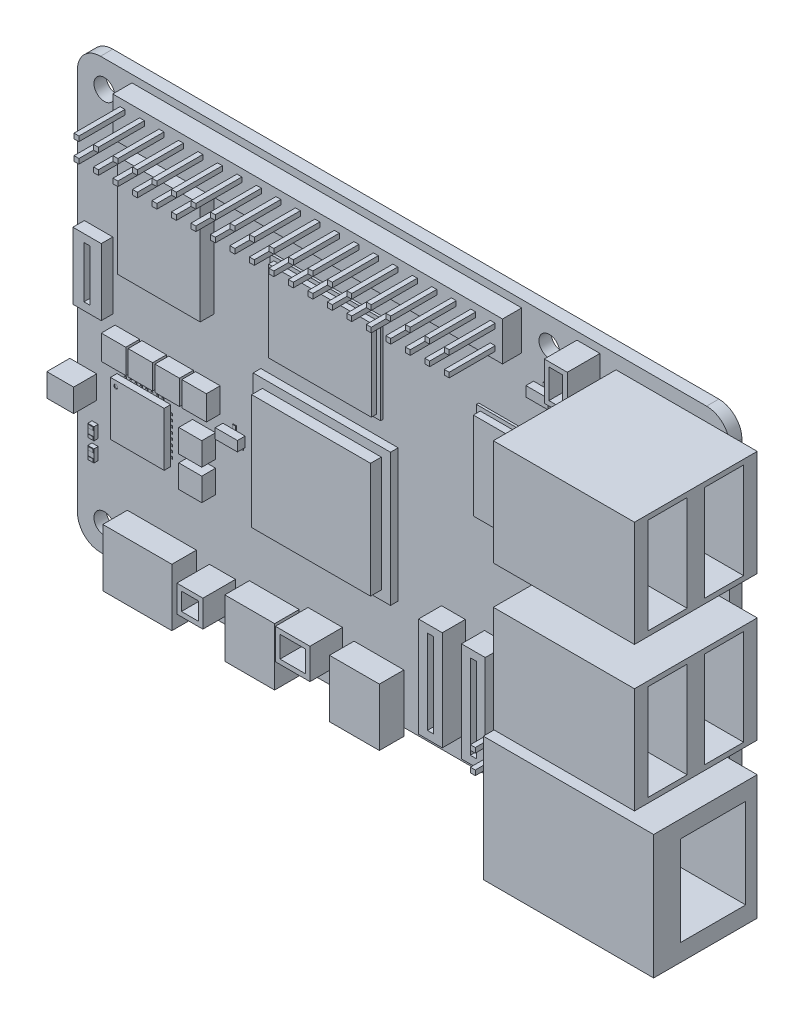
SolidWorks part; units mm, degrees
ref_plane "Front Plane" through (0, 0, 0) normal (0, 0, 1) x (1, 0, 0)
ref_plane "Top Plane" through (0, 0, 0) normal (0, 1, 0) x (1, 0, 0)
ref_plane "Right Plane" through (0, 0, 0) normal (1, 0, 0) x (0, 0, -1)
sketch "Sketch1" plane through (0, 0, 0) normal (0, 0, 1) x (1, 0, 0)
  line L0 (3, 0) -> (82, 0)
  line L1 (85, 3) -> (85, 53)
  line L2 (82, 56) -> (3, 56)
  line L3 (0, 53) -> (0, 3)
  arc A0 (82, 0) -> (85, 3) centre (82, 3) ccw
  arc A1 (85, 53) -> (82, 56) centre (82, 53) ccw
  arc A2 (3, 56) -> (0, 53) centre (3, 53) ccw
  arc A3 (0, 3) -> (3, 0) centre (3, 3) ccw
extrude "PCB" add sketch "Sketch1" along normal blind 1.6
ref_plane "Plane_z1_6" through (0, 0, 1.6) normal (0, 0, 1) x (1, 0, 0)
sketch "Sketch2" plane through (0, 0, 1.6) normal (0, 0, 1) x (1, 0, 0)
  line L1 (7.1, 49.96) -> (57.9, 49.96)
  line L2 (7.1, 49.96) -> (7.1, 55.04)
  line L3 (7.1, 55.04) -> (57.9, 55.04)
  line L4 (57.9, 49.96) -> (57.9, 55.04)
  line L6 (58.76, 6.76) -> (63.84, 6.76)
  line L7 (58.76, 6.76) -> (58.76, 11.84)
  line L8 (58.76, 11.84) -> (63.84, 11.84)
  line L9 (63.84, 6.76) -> (63.84, 11.84)
extrude "Header_Blocks" add sketch "Sketch2" along normal blind 2.5
ref_plane "Plane_z4_1" through (0, 0, 4.1) normal (0, 0, 1) x (1, 0, 0)
sketch "Sketch3" plane through (0, 0, 4.1) normal (0, 0, 1) x (1, 0, 0)
  line L1 (8.05, 50.91) -> (8.69, 50.91)
  line L2 (8.05, 50.91) -> (8.05, 51.55)
  line L3 (8.05, 51.55) -> (8.69, 51.55)
  line L4 (8.69, 50.91) -> (8.69, 51.55)
  line L6 (8.05, 53.45) -> (8.69, 53.45)
  line L7 (8.05, 53.45) -> (8.05, 54.09)
  line L8 (8.05, 54.09) -> (8.69, 54.09)
  line L9 (8.69, 53.45) -> (8.69, 54.09)
  line L11 (10.59, 50.91) -> (11.23, 50.91)
  line L12 (10.59, 50.91) -> (10.59, 51.55)
  line L13 (10.59, 51.55) -> (11.23, 51.55)
  line L14 (11.23, 50.91) -> (11.23, 51.55)
  line L16 (10.59, 53.45) -> (11.23, 53.45)
  line L17 (10.59, 53.45) -> (10.59, 54.09)
  line L18 (10.59, 54.09) -> (11.23, 54.09)
  line L19 (11.23, 53.45) -> (11.23, 54.09)
  line L21 (13.13, 50.91) -> (13.77, 50.91)
  line L22 (13.13, 50.91) -> (13.13, 51.55)
  line L23 (13.13, 51.55) -> (13.77, 51.55)
  line L24 (13.77, 50.91) -> (13.77, 51.55)
  line L26 (13.13, 53.45) -> (13.77, 53.45)
  line L27 (13.13, 53.45) -> (13.13, 54.09)
  line L28 (13.13, 54.09) -> (13.77, 54.09)
  line L29 (13.77, 53.45) -> (13.77, 54.09)
  line L31 (15.67, 50.91) -> (16.31, 50.91)
  line L32 (15.67, 50.91) -> (15.67, 51.55)
  line L33 (15.67, 51.55) -> (16.31, 51.55)
  line L34 (16.31, 50.91) -> (16.31, 51.55)
  line L36 (15.67, 53.45) -> (16.31, 53.45)
  line L37 (15.67, 53.45) -> (15.67, 54.09)
  line L38 (15.67, 54.09) -> (16.31, 54.09)
  line L39 (16.31, 53.45) -> (16.31, 54.09)
  line L41 (18.21, 50.91) -> (18.85, 50.91)
  line L42 (18.21, 50.91) -> (18.21, 51.55)
  line L43 (18.21, 51.55) -> (18.85, 51.55)
  line L44 (18.85, 50.91) -> (18.85, 51.55)
  line L46 (18.21, 53.45) -> (18.85, 53.45)
  line L47 (18.21, 53.45) -> (18.21, 54.09)
  line L48 (18.21, 54.09) -> (18.85, 54.09)
  line L49 (18.85, 53.45) -> (18.85, 54.09)
  line L51 (20.75, 50.91) -> (21.39, 50.91)
  line L52 (20.75, 50.91) -> (20.75, 51.55)
  line L53 (20.75, 51.55) -> (21.39, 51.55)
  line L54 (21.39, 50.91) -> (21.39, 51.55)
  line L56 (20.75, 53.45) -> (21.39, 53.45)
  line L57 (20.75, 53.45) -> (20.75, 54.09)
  line L58 (20.75, 54.09) -> (21.39, 54.09)
  line L59 (21.39, 53.45) -> (21.39, 54.09)
  line L61 (23.29, 50.91) -> (23.93, 50.91)
  line L62 (23.29, 50.91) -> (23.29, 51.55)
  line L63 (23.29, 51.55) -> (23.93, 51.55)
  line L64 (23.93, 50.91) -> (23.93, 51.55)
  line L66 (23.29, 53.45) -> (23.93, 53.45)
  line L67 (23.29, 53.45) -> (23.29, 54.09)
  line L68 (23.29, 54.09) -> (23.93, 54.09)
  line L69 (23.93, 53.45) -> (23.93, 54.09)
  line L71 (25.83, 50.91) -> (26.47, 50.91)
  line L72 (25.83, 50.91) -> (25.83, 51.55)
  line L73 (25.83, 51.55) -> (26.47, 51.55)
  line L74 (26.47, 50.91) -> (26.47, 51.55)
  line L76 (25.83, 53.45) -> (26.47, 53.45)
  line L77 (25.83, 53.45) -> (25.83, 54.09)
  line L78 (25.83, 54.09) -> (26.47, 54.09)
  line L79 (26.47, 53.45) -> (26.47, 54.09)
  line L81 (28.37, 50.91) -> (29.01, 50.91)
  line L82 (28.37, 50.91) -> (28.37, 51.55)
  line L83 (28.37, 51.55) -> (29.01, 51.55)
  line L84 (29.01, 50.91) -> (29.01, 51.55)
  line L86 (28.37, 53.45) -> (29.01, 53.45)
  line L87 (28.37, 53.45) -> (28.37, 54.09)
  line L88 (28.37, 54.09) -> (29.01, 54.09)
  line L89 (29.01, 53.45) -> (29.01, 54.09)
  line L91 (30.91, 50.91) -> (31.55, 50.91)
  line L92 (30.91, 50.91) -> (30.91, 51.55)
  line L93 (30.91, 51.55) -> (31.55, 51.55)
  line L94 (31.55, 50.91) -> (31.55, 51.55)
  line L96 (30.91, 53.45) -> (31.55, 53.45)
  line L97 (30.91, 53.45) -> (30.91, 54.09)
  line L98 (30.91, 54.09) -> (31.55, 54.09)
  line L99 (31.55, 53.45) -> (31.55, 54.09)
  line L101 (33.45, 50.91) -> (34.09, 50.91)
  line L102 (33.45, 50.91) -> (33.45, 51.55)
  line L103 (33.45, 51.55) -> (34.09, 51.55)
  line L104 (34.09, 50.91) -> (34.09, 51.55)
  line L106 (33.45, 53.45) -> (34.09, 53.45)
  line L107 (33.45, 53.45) -> (33.45, 54.09)
  line L108 (33.45, 54.09) -> (34.09, 54.09)
  line L109 (34.09, 53.45) -> (34.09, 54.09)
  line L111 (35.99, 50.91) -> (36.63, 50.91)
  line L112 (35.99, 50.91) -> (35.99, 51.55)
  line L113 (35.99, 51.55) -> (36.63, 51.55)
  line L114 (36.63, 50.91) -> (36.63, 51.55)
  line L116 (35.99, 53.45) -> (36.63, 53.45)
  line L117 (35.99, 53.45) -> (35.99, 54.09)
  line L118 (35.99, 54.09) -> (36.63, 54.09)
  line L119 (36.63, 53.45) -> (36.63, 54.09)
  line L121 (38.53, 50.91) -> (39.17, 50.91)
  line L122 (38.53, 50.91) -> (38.53, 51.55)
  line L123 (38.53, 51.55) -> (39.17, 51.55)
  line L124 (39.17, 50.91) -> (39.17, 51.55)
  line L126 (38.53, 53.45) -> (39.17, 53.45)
  line L127 (38.53, 53.45) -> (38.53, 54.09)
  line L128 (38.53, 54.09) -> (39.17, 54.09)
  line L129 (39.17, 53.45) -> (39.17, 54.09)
  line L131 (41.07, 50.91) -> (41.71, 50.91)
  line L132 (41.07, 50.91) -> (41.07, 51.55)
  line L133 (41.07, 51.55) -> (41.71, 51.55)
  line L134 (41.71, 50.91) -> (41.71, 51.55)
  line L136 (41.07, 53.45) -> (41.71, 53.45)
  line L137 (41.07, 53.45) -> (41.07, 54.09)
  line L138 (41.07, 54.09) -> (41.71, 54.09)
  line L139 (41.71, 53.45) -> (41.71, 54.09)
  line L141 (43.61, 50.91) -> (44.25, 50.91)
  line L142 (43.61, 50.91) -> (43.61, 51.55)
  line L143 (43.61, 51.55) -> (44.25, 51.55)
  line L144 (44.25, 50.91) -> (44.25, 51.55)
  line L146 (43.61, 53.45) -> (44.25, 53.45)
  line L147 (43.61, 53.45) -> (43.61, 54.09)
  line L148 (43.61, 54.09) -> (44.25, 54.09)
  line L149 (44.25, 53.45) -> (44.25, 54.09)
  line L151 (46.15, 50.91) -> (46.79, 50.91)
  line L152 (46.15, 50.91) -> (46.15, 51.55)
  line L153 (46.15, 51.55) -> (46.79, 51.55)
  line L154 (46.79, 50.91) -> (46.79, 51.55)
  line L156 (46.15, 53.45) -> (46.79, 53.45)
  line L157 (46.15, 53.45) -> (46.15, 54.09)
  line L158 (46.15, 54.09) -> (46.79, 54.09)
  line L159 (46.79, 53.45) -> (46.79, 54.09)
  line L161 (48.69, 50.91) -> (49.33, 50.91)
  line L162 (48.69, 50.91) -> (48.69, 51.55)
  line L163 (48.69, 51.55) -> (49.33, 51.55)
  line L164 (49.33, 50.91) -> (49.33, 51.55)
  line L166 (48.69, 53.45) -> (49.33, 53.45)
  line L167 (48.69, 53.45) -> (48.69, 54.09)
  line L168 (48.69, 54.09) -> (49.33, 54.09)
  line L169 (49.33, 53.45) -> (49.33, 54.09)
  line L171 (51.23, 50.91) -> (51.87, 50.91)
  line L172 (51.23, 50.91) -> (51.23, 51.55)
  line L173 (51.23, 51.55) -> (51.87, 51.55)
  line L174 (51.87, 50.91) -> (51.87, 51.55)
  line L176 (51.23, 53.45) -> (51.87, 53.45)
  line L177 (51.23, 53.45) -> (51.23, 54.09)
  line L178 (51.23, 54.09) -> (51.87, 54.09)
  line L179 (51.87, 53.45) -> (51.87, 54.09)
  line L181 (53.77, 50.91) -> (54.41, 50.91)
  line L182 (53.77, 50.91) -> (53.77, 51.55)
  line L183 (53.77, 51.55) -> (54.41, 51.55)
  line L184 (54.41, 50.91) -> (54.41, 51.55)
  line L186 (53.77, 53.45) -> (54.41, 53.45)
  line L187 (53.77, 53.45) -> (53.77, 54.09)
  line L188 (53.77, 54.09) -> (54.41, 54.09)
  line L189 (54.41, 53.45) -> (54.41, 54.09)
  line L191 (56.31, 50.91) -> (56.95, 50.91)
  line L192 (56.31, 50.91) -> (56.31, 51.55)
  line L193 (56.31, 51.55) -> (56.95, 51.55)
  line L194 (56.95, 50.91) -> (56.95, 51.55)
  line L196 (56.31, 53.45) -> (56.95, 53.45)
  line L197 (56.31, 53.45) -> (56.31, 54.09)
  line L198 (56.31, 54.09) -> (56.95, 54.09)
  line L199 (56.95, 53.45) -> (56.95, 54.09)
  line L201 (59.71, 7.71) -> (60.35, 7.71)
  line L202 (59.71, 7.71) -> (59.71, 8.35)
  line L203 (59.71, 8.35) -> (60.35, 8.35)
  line L204 (60.35, 7.71) -> (60.35, 8.35)
  line L206 (59.71, 10.25) -> (60.35, 10.25)
  line L207 (59.71, 10.25) -> (59.71, 10.89)
  line L208 (59.71, 10.89) -> (60.35, 10.89)
  line L209 (60.35, 10.25) -> (60.35, 10.89)
  line L211 (62.25, 7.71) -> (62.89, 7.71)
  line L212 (62.25, 7.71) -> (62.25, 8.35)
  line L213 (62.25, 8.35) -> (62.89, 8.35)
  line L214 (62.89, 7.71) -> (62.89, 8.35)
  line L216 (62.25, 10.25) -> (62.89, 10.25)
  line L217 (62.25, 10.25) -> (62.25, 10.89)
  line L218 (62.25, 10.89) -> (62.89, 10.89)
  line L219 (62.89, 10.25) -> (62.89, 10.89)
extrude "Header_Pins" add sketch "Sketch3" along normal blind 6
sketch "Sketch4" plane through (0, 0, 1.6) normal (0, 0, 1) x (1, 0, 0)
  line L1 (6.125, 14.1) -> (6.375, 14.1)
  line L2 (6.125, 14.1) -> (6.125, 14.4)
  line L3 (6.125, 14.4) -> (6.375, 14.4)
  line L4 (6.375, 14.1) -> (6.375, 14.4)
  line L6 (5, 15.225) -> (5.3, 15.225)
  line L7 (5, 15.225) -> (5, 15.475)
  line L8 (5, 15.475) -> (5.3, 15.475)
  line L9 (5.3, 15.225) -> (5.3, 15.475)
  line L11 (6.125, 21.2) -> (6.375, 21.2)
  line L12 (6.125, 21.2) -> (6.125, 21.5)
  line L13 (6.125, 21.5) -> (6.375, 21.5)
  line L14 (6.375, 21.2) -> (6.375, 21.5)
  line L16 (12.1, 15.225) -> (12.4, 15.225)
  line L17 (12.1, 15.225) -> (12.1, 15.475)
  line L18 (12.1, 15.475) -> (12.4, 15.475)
  line L19 (12.4, 15.225) -> (12.4, 15.475)
  line L21 (6.825, 14.1) -> (7.075, 14.1)
  line L22 (6.825, 14.1) -> (6.825, 14.4)
  line L23 (6.825, 14.4) -> (7.075, 14.4)
  line L24 (7.075, 14.1) -> (7.075, 14.4)
  line L26 (5, 15.925) -> (5.3, 15.925)
  line L27 (5, 15.925) -> (5, 16.175)
  line L28 (5, 16.175) -> (5.3, 16.175)
  line L29 (5.3, 15.925) -> (5.3, 16.175)
  line L31 (6.825, 21.2) -> (7.075, 21.2)
  line L32 (6.825, 21.2) -> (6.825, 21.5)
  line L33 (6.825, 21.5) -> (7.075, 21.5)
  line L34 (7.075, 21.2) -> (7.075, 21.5)
  line L36 (12.1, 15.925) -> (12.4, 15.925)
  line L37 (12.1, 15.925) -> (12.1, 16.175)
  line L38 (12.1, 16.175) -> (12.4, 16.175)
  line L39 (12.4, 15.925) -> (12.4, 16.175)
  line L41 (7.525, 14.1) -> (7.775, 14.1)
  line L42 (7.525, 14.1) -> (7.525, 14.4)
  line L43 (7.525, 14.4) -> (7.775, 14.4)
  line L44 (7.775, 14.1) -> (7.775, 14.4)
  line L46 (5, 16.625) -> (5.3, 16.625)
  line L47 (5, 16.625) -> (5, 16.875)
  line L48 (5, 16.875) -> (5.3, 16.875)
  line L49 (5.3, 16.625) -> (5.3, 16.875)
  line L51 (7.525, 21.2) -> (7.775, 21.2)
  line L52 (7.525, 21.2) -> (7.525, 21.5)
  line L53 (7.525, 21.5) -> (7.775, 21.5)
  line L54 (7.775, 21.2) -> (7.775, 21.5)
  line L56 (12.1, 16.625) -> (12.4, 16.625)
  line L57 (12.1, 16.625) -> (12.1, 16.875)
  line L58 (12.1, 16.875) -> (12.4, 16.875)
  line L59 (12.4, 16.625) -> (12.4, 16.875)
  line L61 (8.225, 14.1) -> (8.475, 14.1)
  line L62 (8.225, 14.1) -> (8.225, 14.4)
  line L63 (8.225, 14.4) -> (8.475, 14.4)
  line L64 (8.475, 14.1) -> (8.475, 14.4)
  line L66 (5, 17.325) -> (5.3, 17.325)
  line L67 (5, 17.325) -> (5, 17.575)
  line L68 (5, 17.575) -> (5.3, 17.575)
  line L69 (5.3, 17.325) -> (5.3, 17.575)
  line L71 (8.225, 21.2) -> (8.475, 21.2)
  line L72 (8.225, 21.2) -> (8.225, 21.5)
  line L73 (8.225, 21.5) -> (8.475, 21.5)
  line L74 (8.475, 21.2) -> (8.475, 21.5)
  line L76 (12.1, 17.325) -> (12.4, 17.325)
  line L77 (12.1, 17.325) -> (12.1, 17.575)
  line L78 (12.1, 17.575) -> (12.4, 17.575)
  line L79 (12.4, 17.325) -> (12.4, 17.575)
  line L81 (8.925, 14.1) -> (9.175, 14.1)
  line L82 (8.925, 14.1) -> (8.925, 14.4)
  line L83 (8.925, 14.4) -> (9.175, 14.4)
  line L84 (9.175, 14.1) -> (9.175, 14.4)
  line L86 (5, 18.025) -> (5.3, 18.025)
  line L87 (5, 18.025) -> (5, 18.275)
  line L88 (5, 18.275) -> (5.3, 18.275)
  line L89 (5.3, 18.025) -> (5.3, 18.275)
  line L91 (8.925, 21.2) -> (9.175, 21.2)
  line L92 (8.925, 21.2) -> (8.925, 21.5)
  line L93 (8.925, 21.5) -> (9.175, 21.5)
  line L94 (9.175, 21.2) -> (9.175, 21.5)
  line L96 (12.1, 18.025) -> (12.4, 18.025)
  line L97 (12.1, 18.025) -> (12.1, 18.275)
  line L98 (12.1, 18.275) -> (12.4, 18.275)
  line L99 (12.4, 18.025) -> (12.4, 18.275)
  line L101 (9.625, 14.1) -> (9.875, 14.1)
  line L102 (9.625, 14.1) -> (9.625, 14.4)
  line L103 (9.625, 14.4) -> (9.875, 14.4)
  line L104 (9.875, 14.1) -> (9.875, 14.4)
  line L106 (5, 18.725) -> (5.3, 18.725)
  line L107 (5, 18.725) -> (5, 18.975)
  line L108 (5, 18.975) -> (5.3, 18.975)
  line L109 (5.3, 18.725) -> (5.3, 18.975)
  line L111 (9.625, 21.2) -> (9.875, 21.2)
  line L112 (9.625, 21.2) -> (9.625, 21.5)
  line L113 (9.625, 21.5) -> (9.875, 21.5)
  line L114 (9.875, 21.2) -> (9.875, 21.5)
  line L116 (12.1, 18.725) -> (12.4, 18.725)
  line L117 (12.1, 18.725) -> (12.1, 18.975)
  line L118 (12.1, 18.975) -> (12.4, 18.975)
  line L119 (12.4, 18.725) -> (12.4, 18.975)
  line L121 (10.325, 14.1) -> (10.575, 14.1)
  line L122 (10.325, 14.1) -> (10.325, 14.4)
  line L123 (10.325, 14.4) -> (10.575, 14.4)
  line L124 (10.575, 14.1) -> (10.575, 14.4)
  line L126 (5, 19.425) -> (5.3, 19.425)
  line L127 (5, 19.425) -> (5, 19.675)
  line L128 (5, 19.675) -> (5.3, 19.675)
  line L129 (5.3, 19.425) -> (5.3, 19.675)
  line L131 (10.325, 21.2) -> (10.575, 21.2)
  line L132 (10.325, 21.2) -> (10.325, 21.5)
  line L133 (10.325, 21.5) -> (10.575, 21.5)
  line L134 (10.575, 21.2) -> (10.575, 21.5)
  line L136 (12.1, 19.425) -> (12.4, 19.425)
  line L137 (12.1, 19.425) -> (12.1, 19.675)
  line L138 (12.1, 19.675) -> (12.4, 19.675)
  line L139 (12.4, 19.425) -> (12.4, 19.675)
  line L141 (11.025, 14.1) -> (11.275, 14.1)
  line L142 (11.025, 14.1) -> (11.025, 14.4)
  line L143 (11.025, 14.4) -> (11.275, 14.4)
  line L144 (11.275, 14.1) -> (11.275, 14.4)
  line L146 (5, 20.125) -> (5.3, 20.125)
  line L147 (5, 20.125) -> (5, 20.375)
  line L148 (5, 20.375) -> (5.3, 20.375)
  line L149 (5.3, 20.125) -> (5.3, 20.375)
  line L151 (11.025, 21.2) -> (11.275, 21.2)
  line L152 (11.025, 21.2) -> (11.025, 21.5)
  line L153 (11.025, 21.5) -> (11.275, 21.5)
  line L154 (11.275, 21.2) -> (11.275, 21.5)
  line L156 (12.1, 20.125) -> (12.4, 20.125)
  line L157 (12.1, 20.125) -> (12.1, 20.375)
  line L158 (12.1, 20.375) -> (12.4, 20.375)
  line L159 (12.4, 20.125) -> (12.4, 20.375)
  line L161 (66.275, 43.15) -> (66.525, 43.15)
  line L162 (66.275, 43.15) -> (66.275, 43.45)
  line L163 (66.275, 43.45) -> (66.525, 43.45)
  line L164 (66.525, 43.15) -> (66.525, 43.45)
  line L166 (65.2, 44.475) -> (65.5, 44.475)
  line L167 (65.2, 44.475) -> (65.2, 44.725)
  line L168 (65.2, 44.725) -> (65.5, 44.725)
  line L169 (65.5, 44.475) -> (65.5, 44.725)
  line L171 (66.275, 47.75) -> (66.525, 47.75)
  line L172 (66.275, 47.75) -> (66.275, 48.05)
  line L173 (66.275, 48.05) -> (66.525, 48.05)
  line L174 (66.525, 47.75) -> (66.525, 48.05)
  line L176 (69.3, 44.475) -> (69.6, 44.475)
  line L177 (69.3, 44.475) -> (69.3, 44.725)
  line L178 (69.3, 44.725) -> (69.6, 44.725)
  line L179 (69.6, 44.475) -> (69.6, 44.725)
  line L181 (66.9417, 43.15) -> (67.1917, 43.15)
  line L182 (66.9417, 43.15) -> (66.9417, 43.45)
  line L183 (66.9417, 43.45) -> (67.1917, 43.45)
  line L184 (67.1917, 43.15) -> (67.1917, 43.45)
  line L186 (65.2, 45.1417) -> (65.5, 45.1417)
  line L187 (65.2, 45.1417) -> (65.2, 45.3917)
  line L188 (65.2, 45.3917) -> (65.5, 45.3917)
  line L189 (65.5, 45.1417) -> (65.5, 45.3917)
  line L191 (66.9417, 47.75) -> (67.1917, 47.75)
  line L192 (66.9417, 47.75) -> (66.9417, 48.05)
  line L193 (66.9417, 48.05) -> (67.1917, 48.05)
  line L194 (67.1917, 47.75) -> (67.1917, 48.05)
  line L196 (69.3, 45.1417) -> (69.6, 45.1417)
  line L197 (69.3, 45.1417) -> (69.3, 45.3917)
  line L198 (69.3, 45.3917) -> (69.6, 45.3917)
  line L199 (69.6, 45.1417) -> (69.6, 45.3917)
  line L201 (67.6083, 43.15) -> (67.8583, 43.15)
  line L202 (67.6083, 43.15) -> (67.6083, 43.45)
  line L203 (67.6083, 43.45) -> (67.8583, 43.45)
  line L204 (67.8583, 43.15) -> (67.8583, 43.45)
  line L206 (65.2, 45.8083) -> (65.5, 45.8083)
  line L207 (65.2, 45.8083) -> (65.2, 46.0583)
  line L208 (65.2, 46.0583) -> (65.5, 46.0583)
  line L209 (65.5, 45.8083) -> (65.5, 46.0583)
  line L211 (67.6083, 47.75) -> (67.8583, 47.75)
  line L212 (67.6083, 47.75) -> (67.6083, 48.05)
  line L213 (67.6083, 48.05) -> (67.8583, 48.05)
  line L214 (67.8583, 47.75) -> (67.8583, 48.05)
  line L216 (69.3, 45.8083) -> (69.6, 45.8083)
  line L217 (69.3, 45.8083) -> (69.3, 46.0583)
  line L218 (69.3, 46.0583) -> (69.6, 46.0583)
  line L219 (69.6, 45.8083) -> (69.6, 46.0583)
  line L221 (68.275, 43.15) -> (68.525, 43.15)
  line L222 (68.275, 43.15) -> (68.275, 43.45)
  line L223 (68.275, 43.45) -> (68.525, 43.45)
  line L224 (68.525, 43.15) -> (68.525, 43.45)
  line L226 (65.2, 46.475) -> (65.5, 46.475)
  line L227 (65.2, 46.475) -> (65.2, 46.725)
  line L228 (65.2, 46.725) -> (65.5, 46.725)
  line L229 (65.5, 46.475) -> (65.5, 46.725)
  line L231 (68.275, 47.75) -> (68.525, 47.75)
  line L232 (68.275, 47.75) -> (68.275, 48.05)
  line L233 (68.275, 48.05) -> (68.525, 48.05)
  line L234 (68.525, 47.75) -> (68.525, 48.05)
  line L236 (69.3, 46.475) -> (69.6, 46.475)
  line L237 (69.3, 46.475) -> (69.3, 46.725)
  line L238 (69.3, 46.725) -> (69.6, 46.725)
  line L239 (69.6, 46.475) -> (69.6, 46.725)
extrude "Parts_add00" add sketch "Sketch4" along normal blind 0.05
sketch "Sketch5" plane through (0, 0, 1.6) normal (0, 0, 1) x (1, 0, 0)
  line L1 (19.35, 20.85) -> (19.75, 20.85)
  line L2 (19.35, 20.85) -> (19.35, 21.55)
  line L3 (19.35, 21.55) -> (19.75, 21.55)
  line L4 (19.75, 20.85) -> (19.75, 21.55)
  line L6 (21.25, 20.85) -> (21.65, 20.85)
  line L7 (21.25, 20.85) -> (21.25, 21.55)
  line L8 (21.25, 21.55) -> (21.65, 21.55)
  line L9 (21.65, 20.85) -> (21.65, 21.55)
  line L11 (20.3, 22.45) -> (20.7, 22.45)
  line L12 (20.3, 22.45) -> (20.3, 23.15)
  line L13 (20.3, 23.15) -> (20.7, 23.15)
  line L14 (20.7, 22.45) -> (20.7, 23.15)
  line L16 (58.35, 16.85) -> (58.75, 16.85)
  line L17 (58.35, 16.85) -> (58.35, 17.55)
  line L18 (58.35, 17.55) -> (58.75, 17.55)
  line L19 (58.75, 16.85) -> (58.75, 17.55)
  line L21 (60.25, 16.85) -> (60.65, 16.85)
  line L22 (60.25, 16.85) -> (60.25, 17.55)
  line L23 (60.25, 17.55) -> (60.65, 17.55)
  line L24 (60.65, 16.85) -> (60.65, 17.55)
  line L26 (59.3, 18.45) -> (59.7, 18.45)
  line L27 (59.3, 18.45) -> (59.3, 19.15)
  line L28 (59.3, 19.15) -> (59.7, 19.15)
  line L29 (59.7, 18.45) -> (59.7, 19.15)
  line L31 (59.85, 45.85) -> (60.25, 45.85)
  line L32 (59.85, 45.85) -> (59.85, 46.55)
  line L33 (59.85, 46.55) -> (60.25, 46.55)
  line L34 (60.25, 45.85) -> (60.25, 46.55)
  line L36 (61.75, 45.85) -> (62.15, 45.85)
  line L37 (61.75, 45.85) -> (61.75, 46.55)
  line L38 (61.75, 46.55) -> (62.15, 46.55)
  line L39 (62.15, 45.85) -> (62.15, 46.55)
  line L41 (60.8, 47.45) -> (61.2, 47.45)
  line L42 (60.8, 47.45) -> (60.8, 48.15)
  line L43 (60.8, 48.15) -> (61.2, 48.15)
  line L44 (61.2, 47.45) -> (61.2, 48.15)
extrude "Parts_add01" add sketch "Sketch5" along normal blind 0.1
sketch "Sketch6" plane through (0, 0, 1.6) normal (0, 0, 1) x (1, 0, 0)
  line L1 (25.4, 33.4) -> (39.8, 33.4)
  line L2 (25.4, 33.4) -> (25.4, 45)
  line L3 (25.4, 45) -> (39.8, 45)
  line L4 (39.8, 33.4) -> (39.8, 45)
  line L6 (52.3, 29.1) -> (65.2, 29.1)
  line L7 (52.3, 29.1) -> (52.3, 41.5)
  line L8 (52.3, 41.5) -> (65.2, 41.5)
  line L9 (65.2, 29.1) -> (65.2, 41.5)
extrude "Parts_add02" add sketch "Sketch6" along normal blind 0.3
sketch "Sketch7" plane through (0, 0, 1.6) normal (0, 0, 1) x (1, 0, 0)
  line L1 (1.9, 10.2) -> (2.7, 10.2)
  line L2 (1.9, 10.2) -> (1.9, 11.8)
  line L3 (1.9, 11.8) -> (2.7, 11.8)
  line L4 (2.7, 10.2) -> (2.7, 11.8)
  line L6 (1.9, 12.7) -> (2.7, 12.7)
  line L7 (1.9, 12.7) -> (1.9, 14.3)
  line L8 (1.9, 14.3) -> (2.7, 14.3)
  line L9 (2.7, 12.7) -> (2.7, 14.3)
extrude "Parts_add03" add sketch "Sketch7" along normal blind 0.55
sketch "Sketch8" plane through (0, 0, 1.6) normal (0, 0, 1) x (1, 0, 0)
  line L0 (62.7, 19.918) -> (65.882, 23.1)
  line L1 (65.882, 23.1) -> (62.7, 26.282)
  line L2 (62.7, 26.282) -> (59.518, 23.1)
  line L3 (59.518, 23.1) -> (62.7, 19.918)
extrude "Parts_add04" add sketch "Sketch8" along normal blind 0.9
sketch "Sketch9" plane through (0, 0, 1.6) normal (0, 0, 1) x (1, 0, 0)
  line L1 (23.9, 13.9) -> (41.8, 13.9)
  line L2 (23.9, 13.9) -> (23.9, 31.2)
  line L3 (23.9, 31.2) -> (41.8, 31.2)
  line L4 (41.8, 13.9) -> (41.8, 31.2)
extrude "Parts_add05" add sketch "Sketch9" along normal blind 1
sketch "Sketch10" plane through (0, 0, 1.6) normal (0, 0, 1) x (1, 0, 0)
  line L1 (0.9, 27.7) -> (4.6, 27.7)
  line L2 (0.9, 27.7) -> (0.9, 36.4)
  line L3 (0.9, 36.4) -> (4.6, 36.4)
  line L4 (4.6, 27.7) -> (4.6, 36.4)
extrude "Parts_add06" add sketch "Sketch10" along normal blind 1.5
sketch "Sketch11" plane through (0, 0, 1.6) normal (0, 0, 1) x (1, 0, 0)
  line L1 (7, 34.3) -> (17.8, 34.3)
  line L2 (7, 34.3) -> (7, 47.6)
  line L3 (7, 47.6) -> (17.8, 47.6)
  line L4 (17.8, 34.3) -> (17.8, 47.6)
  line L6 (4.9, 23.4) -> (8.1, 23.4)
  line L7 (4.9, 23.4) -> (4.9, 26.6)
  line L8 (4.9, 26.6) -> (8.1, 26.6)
  line L9 (8.1, 23.4) -> (8.1, 26.6)
  line L11 (8.4, 23.4) -> (11.6, 23.4)
  line L12 (8.4, 23.4) -> (8.4, 26.6)
  line L13 (8.4, 26.6) -> (11.6, 26.6)
  line L14 (11.6, 23.4) -> (11.6, 26.6)
  line L16 (11.9, 23.4) -> (15.1, 23.4)
  line L17 (11.9, 23.4) -> (11.9, 26.6)
  line L18 (11.9, 26.6) -> (15.1, 26.6)
  line L19 (15.1, 23.4) -> (15.1, 26.6)
  line L21 (15.4, 23.4) -> (18.6, 23.4)
  line L22 (15.4, 23.4) -> (15.4, 26.6)
  line L23 (15.4, 26.6) -> (18.6, 26.6)
  line L24 (18.6, 23.4) -> (18.6, 26.6)
  line L26 (15, 18) -> (18, 18)
  line L27 (15, 18) -> (15, 21)
  line L28 (15, 21) -> (18, 21)
  line L29 (18, 18) -> (18, 21)
  line L31 (15, 14) -> (18, 14)
  line L32 (15, 14) -> (15, 17)
  line L33 (15, 17) -> (18, 17)
  line L34 (18, 14) -> (18, 17)
extrude "Parts_add07" add sketch "Sketch11" along normal blind 1.8
sketch "Sketch12" plane through (0, 0, 1.6) normal (0, 0, 1) x (1, 0, 0)
  line L1 (53.05, 3.2) -> (56.15, 3.2)
  line L2 (53.05, 3.2) -> (53.05, 16.2)
  line L3 (53.05, 16.2) -> (56.15, 16.2)
  line L4 (56.15, 3.2) -> (56.15, 16.2)
  line L6 (47.45, 3.2) -> (50.55, 3.2)
  line L7 (47.45, 3.2) -> (47.45, 16.2)
  line L8 (47.45, 16.2) -> (50.55, 16.2)
  line L9 (50.55, 3.2) -> (50.55, 16.2)
  line L11 (-1, 16.9) -> (2.5, 16.9)
  line L12 (-1, 16.9) -> (-1, 19.9)
  line L13 (-1, 19.9) -> (2.5, 19.9)
  line L14 (2.5, 16.9) -> (2.5, 19.9)
extrude "Parts_add08" add sketch "Sketch12" along normal blind 3
sketch "Sketch13" plane through (0, 0, 1.6) normal (0, 0, 1) x (1, 0, 0)
  line L1 (22.4, -1) -> (28.9, -1)
  line L2 (22.4, -1) -> (22.4, 6.5)
  line L3 (22.4, 6.5) -> (28.9, 6.5)
  line L4 (28.9, -1) -> (28.9, 6.5)
  line L6 (36.05, -1) -> (42.55, -1)
  line L7 (36.05, -1) -> (36.05, 6.5)
  line L8 (36.05, 6.5) -> (42.55, 6.5)
  line L9 (42.55, -1) -> (42.55, 6.5)
  line L11 (6.5, -1) -> (15.5, -1)
  line L12 (6.5, -1) -> (6.5, 6.5)
  line L13 (6.5, 6.5) -> (15.5, 6.5)
  line L14 (15.5, -1) -> (15.5, 6.5)
extrude "Parts_add09" add sketch "Sketch13" along normal blind 3.2
sketch "Sketch14" plane through (0, 0, 1.6) normal (0, 0, 1) x (1, 0, 0)
  line L1 (65.1, 50) -> (68.1, 50)
  line L2 (65.1, 50) -> (65.1, 55)
  line L3 (65.1, 55) -> (68.1, 55)
  line L4 (68.1, 50) -> (68.1, 55)
  line L6 (30.05, 3.3) -> (34.55, 3.3)
  line L7 (30.05, 3.3) -> (30.05, 7.3)
  line L8 (30.05, 7.3) -> (34.55, 7.3)
  line L9 (34.55, 3.3) -> (34.55, 7.3)
  line L11 (17.2, 2.25) -> (20.6, 2.25)
  line L12 (17.2, 2.25) -> (17.2, 5.75)
  line L13 (17.2, 5.75) -> (20.6, 5.75)
  line L14 (20.6, 2.25) -> (20.6, 5.75)
extrude "Parts_add10" add sketch "Sketch14" along normal blind 4.25
sketch "Sketch15" plane through (0, 0, 1.6) normal (0, 0, 1) x (1, 0, 0)
  line L1 (66.4, 1.5) -> (88.6, 1.5)
  line L2 (66.4, 1.5) -> (66.4, 17.7)
  line L3 (66.4, 17.7) -> (88.6, 17.7)
  line L4 (88.6, 1.5) -> (88.6, 17.7)
extrude "Parts_add11" add sketch "Sketch15" along normal blind 13.5
sketch "Sketch16" plane through (0, 0, 1.6) normal (0, 0, 1) x (1, 0, 0)
  line L1 (70.2, 40.4) -> (88.6, 40.4)
  line L2 (70.2, 40.4) -> (70.2, 54.2)
  line L3 (70.2, 54.2) -> (88.6, 54.2)
  line L4 (88.6, 40.4) -> (88.6, 54.2)
  line L6 (70.2, 21.6) -> (88.6, 21.6)
  line L7 (70.2, 21.6) -> (70.2, 35.4)
  line L8 (70.2, 35.4) -> (88.6, 35.4)
  line L9 (88.6, 21.6) -> (88.6, 35.4)
extrude "Parts_add12" add sketch "Sketch16" along normal blind 16
ref_plane "Plane_z1_65" through (0, 0, 1.65) normal (0, 0, 1) x (1, 0, 0)
sketch "Sketch17" plane through (0, 0, 1.65) normal (0, 0, 1) x (1, 0, 0)
  line L1 (5.2, 14.3) -> (12.2, 14.3)
  line L2 (5.2, 14.3) -> (5.2, 21.3)
  line L3 (5.2, 21.3) -> (12.2, 21.3)
  line L4 (12.2, 14.3) -> (12.2, 21.3)
extrude "Parts_add13" add sketch "Sketch17" along normal blind 0.85
sketch "Sketch18" plane through (0, 0, 1.65) normal (0, 0, 1) x (1, 0, 0)
  line L1 (65.4, 43.35) -> (69.4, 43.35)
  line L2 (65.4, 43.35) -> (65.4, 47.85)
  line L3 (65.4, 47.85) -> (69.4, 47.85)
  line L4 (69.4, 43.35) -> (69.4, 47.85)
extrude "Parts_add14" add sketch "Sketch18" along normal blind 0.95
ref_plane "Plane_z1_7" through (0, 0, 1.7) normal (0, 0, 1) x (1, 0, 0)
sketch "Sketch19" plane through (0, 0, 1.7) normal (0, 0, 1) x (1, 0, 0)
  line L1 (19.05, 21.35) -> (21.95, 21.35)
  line L2 (19.05, 21.35) -> (19.05, 22.65)
  line L3 (19.05, 22.65) -> (21.95, 22.65)
  line L4 (21.95, 21.35) -> (21.95, 22.65)
  line L6 (58.05, 17.35) -> (60.95, 17.35)
  line L7 (58.05, 17.35) -> (58.05, 18.65)
  line L8 (58.05, 18.65) -> (60.95, 18.65)
  line L9 (60.95, 17.35) -> (60.95, 18.65)
  line L11 (59.55, 46.35) -> (62.45, 46.35)
  line L12 (59.55, 46.35) -> (59.55, 47.65)
  line L13 (59.55, 47.65) -> (62.45, 47.65)
  line L14 (62.45, 46.35) -> (62.45, 47.65)
extrude "Parts_add15" add sketch "Sketch19" along normal blind 1
ref_plane "Plane_z1_9" through (0, 0, 1.9) normal (0, 0, 1) x (1, 0, 0)
sketch "Sketch20" plane through (0, 0, 1.9) normal (0, 0, 1) x (1, 0, 0)
  line L1 (25.9, 33.9) -> (39.3, 33.9)
  line L2 (25.9, 33.9) -> (25.9, 44.5)
  line L3 (25.9, 44.5) -> (39.3, 44.5)
  line L4 (39.3, 33.9) -> (39.3, 44.5)
extrude "Parts_add16" add sketch "Sketch20" along normal blind 0.7
sketch "Sketch21" plane through (0, 0, 1.9) normal (0, 0, 1) x (1, 0, 0)
  line L1 (52.8, 29.6) -> (64.7, 29.6)
  line L2 (52.8, 29.6) -> (52.8, 41)
  line L3 (52.8, 41) -> (64.7, 41)
  line L4 (64.7, 29.6) -> (64.7, 41)
extrude "Parts_add17" add sketch "Sketch21" along normal blind 0.9
ref_plane "Plane_z2_15" through (0, 0, 2.15) normal (0, 0, 1) x (1, 0, 0)
sketch "Sketch22" plane through (0, 0, 2.15) normal (0, 0, 1) x (1, 0, 0)
  line L1 (1.95, 10.25) -> (2.65, 10.25)
  line L2 (1.95, 10.25) -> (1.95, 10.65)
  line L3 (1.95, 10.65) -> (2.65, 10.65)
  line L4 (2.65, 10.25) -> (2.65, 10.65)
  line L6 (1.95, 11.35) -> (2.65, 11.35)
  line L7 (1.95, 11.35) -> (1.95, 11.75)
  line L8 (1.95, 11.75) -> (2.65, 11.75)
  line L9 (2.65, 11.35) -> (2.65, 11.75)
  line L11 (1.95, 12.75) -> (2.65, 12.75)
  line L12 (1.95, 12.75) -> (1.95, 13.15)
  line L13 (1.95, 13.15) -> (2.65, 13.15)
  line L14 (2.65, 12.75) -> (2.65, 13.15)
  line L16 (1.95, 13.85) -> (2.65, 13.85)
  line L17 (1.95, 13.85) -> (1.95, 14.25)
  line L18 (1.95, 14.25) -> (2.65, 14.25)
  line L19 (2.65, 13.85) -> (2.65, 14.25)
extrude "Parts_add18" add sketch "Sketch22" along normal blind 0.05
ref_plane "Plane_z2_6" through (0, 0, 2.6) normal (0, 0, 1) x (1, 0, 0)
sketch "Sketch23" plane through (0, 0, 2.6) normal (0, 0, 1) x (1, 0, 0)
  line L1 (25.1, 15.05) -> (40.6, 15.05)
  line L2 (25.1, 15.05) -> (25.1, 30.05)
  line L3 (25.1, 30.05) -> (40.6, 30.05)
  line L4 (40.6, 15.05) -> (40.6, 30.05)
extrude "Parts_add19" add sketch "Sketch23" along normal blind 1.4
ref_plane "Plane_x88_6" through (88.6, 0, 0) normal (1, 0, 0) x (0, 0, -1)
sketch "Sketch24" plane through (88.6, 0, 0) normal (1, 0, 0) x (0, 0, -1)
  line L1 (-3.37, 41.05) -> (-8.47, 41.05)
  line L2 (-3.37, 41.05) -> (-3.37, 53.55)
  line L3 (-3.37, 53.55) -> (-8.47, 53.55)
  line L4 (-8.47, 41.05) -> (-8.47, 53.55)
  line L6 (-10.73, 41.05) -> (-15.83, 41.05)
  line L7 (-10.73, 41.05) -> (-10.73, 53.55)
  line L8 (-10.73, 53.55) -> (-15.83, 53.55)
  line L9 (-15.83, 41.05) -> (-15.83, 53.55)
  line L11 (-3.37, 22.25) -> (-8.47, 22.25)
  line L12 (-3.37, 22.25) -> (-3.37, 34.75)
  line L13 (-3.37, 34.75) -> (-8.47, 34.75)
  line L14 (-8.47, 22.25) -> (-8.47, 34.75)
  line L16 (-10.73, 22.25) -> (-15.83, 22.25)
  line L17 (-10.73, 22.25) -> (-10.73, 34.75)
  line L18 (-10.73, 34.75) -> (-15.83, 34.75)
  line L19 (-15.83, 22.25) -> (-15.83, 34.75)
extrude "Parts_cut00" cut sketch "Sketch24" against normal blind 14
sketch "Sketch25" plane through (88.6, 0, 0) normal (1, 0, 0) x (0, 0, -1)
  line L1 (-3.1, 3.75) -> (-11.6, 3.75)
  line L2 (-3.1, 3.75) -> (-3.1, 15.45)
  line L3 (-3.1, 15.45) -> (-11.6, 15.45)
  line L4 (-11.6, 3.75) -> (-11.6, 15.45)
extrude "Parts_cut01" cut sketch "Sketch25" against normal blind 18
ref_plane "Plane_y6" through (0, 6, 0) normal (0, 1, 0) x (1, 0, 0)
sketch "Sketch26" plane through (0, 6, 0) normal (0, 1, 0) x (1, 0, 0)
  line L0 (8.1, -3.2) -> (13.9, -3.2) construction
  line L1 (22.9, -2.2) -> (28.4, -2.2)
  line L2 (22.9, -2.2) -> (22.9, -4.2)
  line L3 (22.9, -4.2) -> (28.4, -4.2)
  line L4 (28.4, -2.2) -> (28.4, -4.2)
  line L5 (8.1, -1.95) -> (13.9, -1.95)
  line L6 (36.55, -2.2) -> (42.05, -2.2)
  line L7 (36.55, -2.2) -> (36.55, -4.2)
  line L8 (36.55, -4.2) -> (42.05, -4.2)
  line L9 (42.05, -2.2) -> (42.05, -4.2)
  line L10 (8.1, -4.45) -> (13.9, -4.45)
  arc A0 (8.1, -1.95) -> (8.1, -4.45) centre (8.1, -3.2) ccw
  arc A1 (13.9, -4.45) -> (13.9, -1.95) centre (13.9, -3.2) ccw
  point P4 (11, -3.2)
  point P13 (0, 0)
extrude "Parts_cut02" cut sketch "Sketch26" against normal blind 7
ref_plane "Plane_z2_5" through (0, 0, 2.5) normal (0, 0, 1) x (1, 0, 0)
sketch "Sketch27" plane through (0, 0, 2.5) normal (0, 0, 1) x (1, 0, 0)
  circle A0 centre (5.9, 20.6) radius 0.25
extrude "Parts_cut03" cut sketch "Sketch27" against normal blind 0.1
sketch "Sketch28" plane through (0, 0, 2.6) normal (0, 0, 1) x (1, 0, 0)
  circle A0 centre (66.1, 47.15) radius 0.25
extrude "Parts_cut04" cut sketch "Sketch28" against normal blind 0.1
ref_plane "Plane_z3_1" through (0, 0, 3.1) normal (0, 0, 1) x (1, 0, 0)
sketch "Sketch29" plane through (0, 0, 3.1) normal (0, 0, 1) x (1, 0, 0)
  line L1 (2.35, 28.7) -> (3.15, 28.7)
  line L2 (2.35, 28.7) -> (2.35, 35.4)
  line L3 (2.35, 35.4) -> (3.15, 35.4)
  line L4 (3.15, 28.7) -> (3.15, 35.4)
extrude "Parts_cut05" cut sketch "Sketch29" against normal blind 1
ref_plane "Plane_z4_6" through (0, 0, 4.6) normal (0, 0, 1) x (1, 0, 0)
sketch "Sketch30" plane through (0, 0, 4.6) normal (0, 0, 1) x (1, 0, 0)
  line L1 (54.2, 4.2) -> (55, 4.2)
  line L2 (54.2, 4.2) -> (54.2, 15.2)
  line L3 (54.2, 15.2) -> (55, 15.2)
  line L4 (55, 4.2) -> (55, 15.2)
  line L6 (48.6, 4.2) -> (49.4, 4.2)
  line L7 (48.6, 4.2) -> (48.6, 15.2)
  line L8 (48.6, 15.2) -> (49.4, 15.2)
  line L9 (49.4, 4.2) -> (49.4, 15.2)
extrude "Parts_cut06" cut sketch "Sketch30" against normal blind 2.5
ref_plane "Plane_z5_85" through (0, 0, 5.85) normal (0, 0, 1) x (1, 0, 0)
sketch "Sketch31" plane through (0, 0, 5.85) normal (0, 0, 1) x (1, 0, 0)
  line L1 (65.7, 50.6) -> (67.5, 50.6)
  line L2 (65.7, 50.6) -> (65.7, 54.4)
  line L3 (65.7, 54.4) -> (67.5, 54.4)
  line L4 (67.5, 50.6) -> (67.5, 54.4)
  line L6 (30.65, 3.9) -> (33.95, 3.9)
  line L7 (30.65, 3.9) -> (30.65, 6.7)
  line L8 (30.65, 6.7) -> (33.95, 6.7)
  line L9 (33.95, 3.9) -> (33.95, 6.7)
  line L11 (17.8, 2.85) -> (20, 2.85)
  line L12 (17.8, 2.85) -> (17.8, 5.15)
  line L13 (17.8, 5.15) -> (20, 5.15)
  line L14 (20, 2.85) -> (20, 5.15)
extrude "Parts_cut07" cut sketch "Sketch31" against normal blind 3.25
sketch "Sketch32" plane through (0, 0, 0) normal (0, 0, 1) x (1, 0, 0)
  circle A0 centre (3.5, 3.5) radius 1.35
  circle A1 centre (3.5, 52.5) radius 1.35
  circle A2 centre (61.5, 3.5) radius 1.35
  circle A3 centre (61.5, 52.5) radius 1.35
extrude "Mount_Holes" cut sketch "Sketch32" against normal through all and the other way through all
equation "\"pcb_l\" = 85mm"
equation "\"pcb_w\" = 56mm"
equation "\"pcb_t\" = 1.6mm"
equation "\"pcb_r\" = 3mm"
equation "\"hole_d\" = 2.7mm"
equation "\"hole_x1\" = 3.5mm"
equation "\"hole_x2\" = 61.5mm"
equation "\"hole_y1\" = 3.5mm"
equation "\"hole_y2\" = 52.5mm"
equation "\"hdr_pitch\" = 2.54mm"
equation "\"hdr_block_h\" = 2.5mm"
equation "\"hdr_pin\" = 0.64mm"
equation "\"hdr_pin_h\" = 6mm"
equation "\"gpio_x\" = 32.5mm"
equation "\"gpio_y\" = 52.5mm"
equation "\"poe_x\" = 61.3mm"
equation "\"poe_y\" = 9.3mm"
equation "\"D1@PCB\" = \"pcb_t\""
